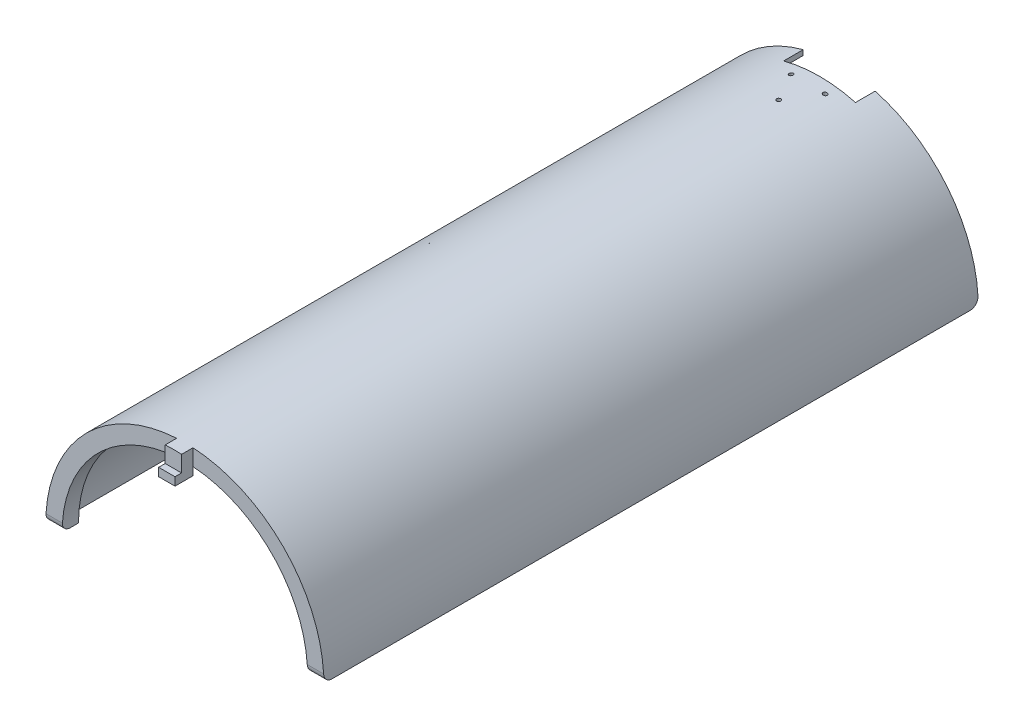
SolidWorks part; units mm, degrees
ref_plane "Front Plane" through (0, 0, 0) normal (0, 0, 1) x (1, 0, 0)
ref_plane "Top Plane" through (0, 0, 0) normal (0, 1, 0) x (1, 0, 0)
ref_plane "Right Plane" through (0, 0, 0) normal (1, 0, 0) x (0, 0, -1)
sketch "Sketch1" plane through (0, 0, 0) normal (0, 0, 1) x (1, 0, 0)
  line L0 (-85, 0) -> (-82, 0)
  line L1 (82, 0) -> (85, 0)
  arc A0 (82, 0) -> (-82, 0) centre (0, 0) ccw
  arc A1 (85, 0) -> (-85, 0) centre (0, 0) ccw
  circle A2 centre (0, 0) radius 85 construction
  circle A3 centre (0, 0) radius 82 construction
  dimension "D1" = 164
  dimension "D2" = 3
extrude "Boss-Extrude1" add sketch "Sketch1" along normal blind 400
sketch "Sketch5" plane through (0, 0, 0) normal (0, 0, -1) x (-1, 0, 0)
  line L0 (-21.9773, 79) -> (21.9773, 79)
  arc A0 (82, 0) -> (-82, 0) centre (0, 0) ccw construction
  arc A1 (85, 0) -> (-85, 0) centre (0, 0) ccw construction
  arc A2 (-21.9773, 79) -> (21.9773, 79) centre (0, 0) cw
  point P8 (0, 85)
  dimension "D1" = 6
extrude "Boss-Extrude3" add sketch "Sketch5" against normal blind 60
fillet "Fillet4" radius 10 1 edges at (0, 79, 60)
sketch "Sketch6" plane through (0, 79, 0) normal (0, -1, 0) x (1, 0, 0)
  line L0 (0, 50) -> (0, 0) construction
  line L1 (21.9773, 50) -> (-21.9773, 50) construction
  line L2 (-2.5, 25) -> (2.5, 25)
  line L3 (21.9773, 50) -> (21.9773, 0) construction
  line L4 (-21.9773, 0) -> (21.9773, 0)
  line L5 (-21.9773, 0) -> (-21.9773, 12)
  line L6 (-21.9773, 12) -> (21.9773, 12)
  line L7 (21.9773, 0) -> (21.9773, 12)
  circle A0 centre (0, 37) radius 1.25
  circle A1 centre (10.3923, 19) radius 1.25
  circle A2 centre (-10.3923, 19) radius 1.25
  point P7 (0, 25)
  point P11 (0, 25)
  point P17 (0, 25)
  dimension "D1" = 2.5
  dimension "D2" = 12
  dimension "D3" = 3
  dimension "D4" = 12
extrude "Cut-Extrude5" cut sketch "Sketch6" against normal blind 50 contours A1 | A2 | A0 L0 | L0 A0 | L0 L6 L1 | L6 L0 L4 L2
sketch "Sketch7" plane through (0, 0, 400) normal (0, 0, 1) x (1, 0, 0)
  line L0 (-75, 0) -> (-82, 0)
  line L1 (75, 0) -> (82, 0)
  arc A0 (-82, 0) -> (82, 0) centre (0, 0) cw
  arc A1 (-75, 0) -> (75, 0) centre (0, 0) cw
  dimension "D1" = 7
extrude "Boss-Extrude4" add sketch "Sketch7" against normal blind 10
sketch "Sketch8" plane through (0, 0, 400) normal (0, 0, 1) x (1, 0, 0)
  line L0 (0, 0) -> (0, 85) construction
  arc A0 (85, 0) -> (-85, 0) centre (0, 0) ccw construction
sketch "Sketch9" plane through (0, 0, 400) normal (0, 0, 1) x (1, 0, 0)
  line L8 (0, 0) -> (0, 85) construction
  line L10 (-5, 80) -> (-5, 70)
  line L11 (-5, 70) -> (5, 70)
  line L12 (5, 80) -> (5, 70)
  line L13 (-5, 80) -> (5, 70) construction
  line L14 (-5, 70) -> (5, 80) construction
  line L15 (-5, 80) -> (-5, 84.8528)
  line L16 (5, 80) -> (5, 84.8528)
  line L19 (-5, 80) -> (-5, 74.8331)
  line L20 (-0.1669, 74.8331) -> (0.1669, 74.8331)
  line L21 (5, 80) -> (5, 74.8331)
  arc A1 (85, 0) -> (-85, 0) centre (0, 0) ccw construction
  arc A4 (-5, 84.8528) -> (5, 84.8528) centre (0, 0) cw
  point P7 (0, 75)
  dimension "D1" = 10
  dimension "D2" = 10
  dimension "D3" = 75
extrude "Boss-Extrude5" add sketch "Sketch9" along normal blind 7
sketch "Sketch10" plane through (0, 0, 407) normal (0, 0, 1) x (1, 0, 0)
  line L0 (5, 84.8528) -> (5, 74.8331) construction
  line L1 (-5, 70) -> (5, 70)
  line L2 (-5, 70) -> (-5, 75)
  line L3 (-5, 75) -> (5, 75)
  line L4 (5, 70) -> (5, 75)
  dimension "D1" = 5
extrude "Boss-Extrude6" add sketch "Sketch10" along normal blind 4
fillet "Fillet6" radius 5 4 edges at (80, 0, 400) (-80, 0, 400) (83.5, 0, 0) (-83.5, 0, 0)
fillet "Fillet7" radius 2 1 edges at (0, 79, 12)
